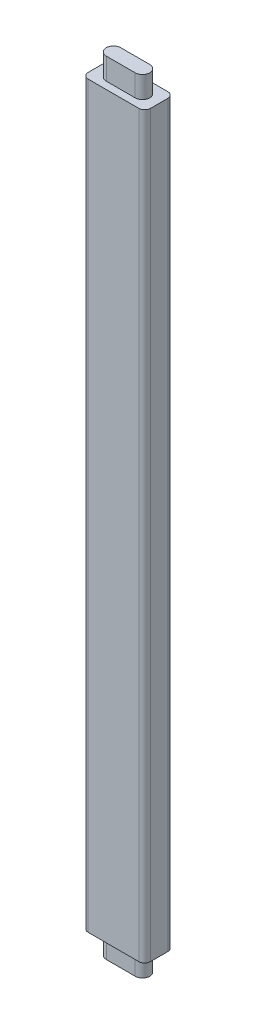
SolidWorks part; units mm, degrees
ref_plane "Front" through (0, 0, 0) normal (0, 0, 1) x (1, 0, 0)
ref_plane "Top" through (0, 0, 0) normal (0, 1, 0) x (1, 0, 0)
ref_plane "Right" through (0, 0, 0) normal (1, 0, 0) x (0, 0, -1)
sketch "Esquisse1" plane through (0, 0, 0) normal (0, 1, 0) x (1, 0, 0)
  line L1 (0, 0) -> (43, 0)
  line L2 (0, 0) -> (0, 20)
  line L3 (0, 20) -> (43, 20)
  line L4 (43, 0) -> (43, 20)
  dimension "D1" = 43
  dimension "D2" = 20
extrude "Boss.-Extru.1" add sketch "Esquisse1" along normal blind 510
sketch "Esquisse2" plane through (0, 510, 0) normal (0, 1, 0) x (1, 0, 0)
  line L0 (43, 10) -> (0, 10) construction
  line L1 (43, 0) -> (43, 20) construction
  line L2 (0, 20) -> (0, 0) construction
  line L3 (11.5, 10) -> (31.5, 10) construction
  line L4 (11.5, 15) -> (31.5, 15)
  line L5 (11.5, 5) -> (31.5, 5)
  arc A0 (11.5, 15) -> (11.5, 5) centre (11.5, 10) ccw
  arc A1 (31.5, 5) -> (31.5, 15) centre (31.5, 10) ccw
  point P8 (21.5, 10)
  dimension "D1" = 10
  dimension "D2" = 20
extrude "Boss.-Extru.2" add sketch "Esquisse2" along normal blind 15
extrude "Boss.-Extru.3" add sketch "Esquisse2<2>" against normal blind 15 from vertex starting at point (43, 0, 0)
sketch "Esquisse2<2>" plane through (0, 510, 0) normal (0, 1, 0) x (1, 0, 0) same geometry as "Esquisse2"
fillet "Congé1" radius 4 4 edges at (43, 255, 0) (43, 255, -20) (0, 255, -20) (0, 255, 0)
